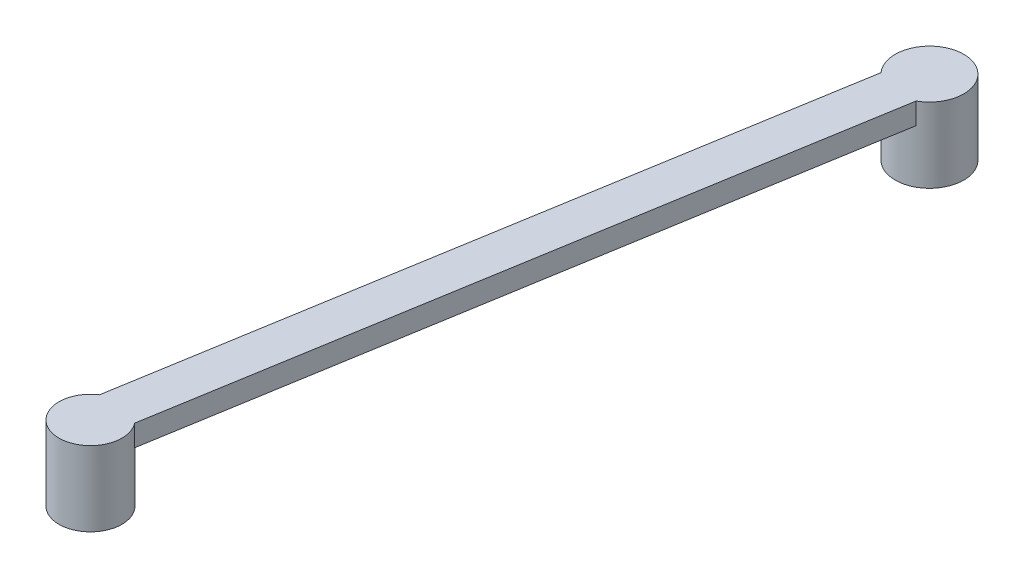
SolidWorks part; units mm, degrees
ref_plane "Front Plane" through (0, 0, 0) normal (0, 0, 1) x (1, 0, 0)
ref_plane "Top Plane" through (0, 0, 0) normal (0, 1, 0) x (1, 0, 0)
ref_plane "Right Plane" through (0, 0, 0) normal (1, 0, 0) x (0, 0, -1)
sketch "Sketch1" plane through (0, 0, 0) normal (0, 1, 0) x (1, 0, 0)
  line L5 (-514.947, 8.8684) -> (-509.7117, 40.2401)
  line L6 (-516.9197, 9.1976) -> (-511.6844, 40.5693)
  circle A4 centre (-510.4911, 41.6448) radius 1.6065
  circle A5 centre (-516.1118, 7.9639) radius 1.4747
extrude "Boss-Extrude1" add sketch "Sketch1" along normal blind 1 contours A5 L5 A4 L6 | A4 | A5
extrude "Boss-Extrude2" add sketch "Sketch1<3>" against normal blind 2.5 contours A5 | A4 region at (-516.1118, 0, -7.9639) region at (-510.4911, 0, -41.6448)
sketch "Sketch1<3>" plane through (0, 0, 0) normal (0, 1, 0) x (1, 0, 0) same geometry as "Sketch1"
